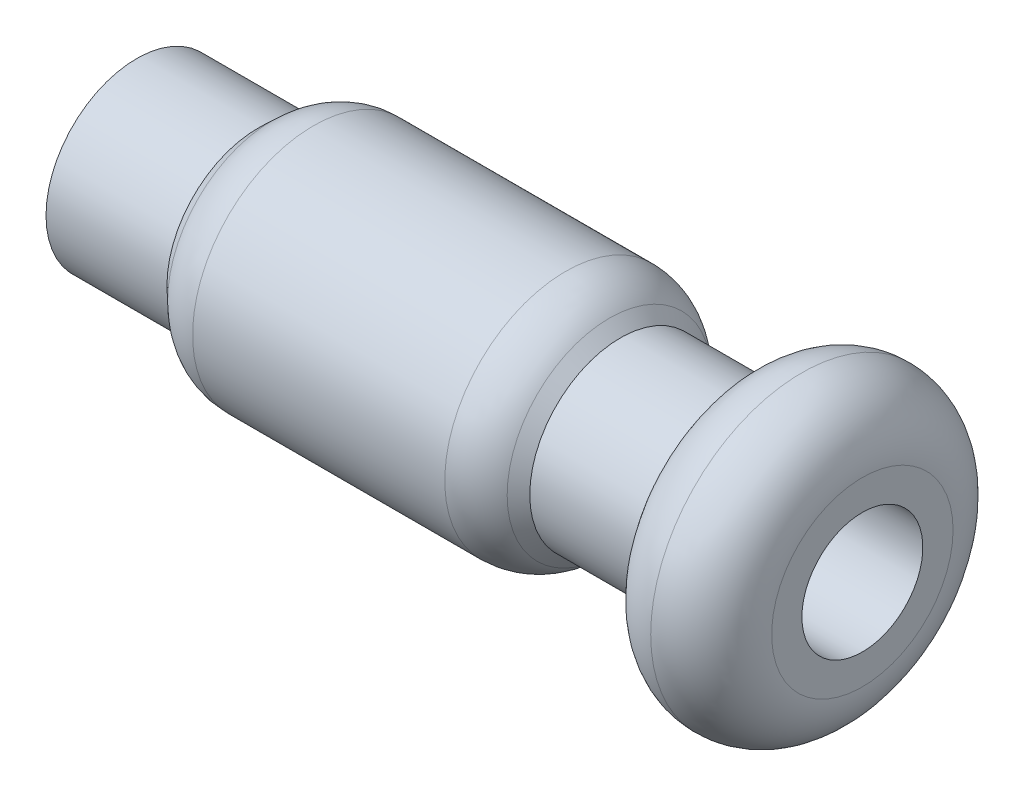
SolidWorks part; units mm, degrees
ref_plane "Front Plane" through (0, 0, 0) normal (0, 0, 1) x (1, 0, 0)
ref_plane "Top Plane" through (0, 0, 0) normal (0, 1, 0) x (1, 0, 0)
ref_plane "Right Plane" through (0, 0, 0) normal (1, 0, 0) x (0, 0, -1)
sketch "Sketch1" plane through (0, 0, 0) normal (0, 0, 1) x (1, 0, 0)
  line L0 (0, 0) -> (10, 0)
  line L1 (10, 0) -> (10, 0.5)
  line L2 (10, 0.5) -> (8, 0.5)
  line L3 (8, 0.5) -> (7.5219, 1)
  line L4 (7.5219, 1) -> (2.5229, 1)
  line L5 (2.5229, 1) -> (2, 0.5)
  line L6 (2, 0.5) -> (0, 0.5)
  line L7 (0, 0.5) -> (0, 0)
  line L8 (-1.4309, -1) -> (12.3178, -1)
  dimension "D1" = 10
  dimension "D2" = 2
  dimension "D3" = 0.5
  dimension "D4" = 1
  dimension "D5" = 1
revolve "Revolve1" add sketch "Sketch1" angle 360 about L8 region at (5.0038, 0.4247, 0)
sketch "Sketch2" plane through (0, 0, 0) normal (0, 0, 1) x (1, 0, 0)
  line L0 (10, -1) -> (12, -1) construction
  line L1 (10, -2.5) -> (10, 0.5) construction
  line L2 (12, -2) -> (12, -3.5)
  line L3 (12, -3.5) -> (10, -3.5)
  line L4 (10, -3.5) -> (10, -2)
  line L5 (10, -2) -> (12, -2)
  point P8 (12.0526, -1)
  point P9 (12.0628, -1)
  dimension "D2" = 1.5
  dimension "D3" = 2
  dimension "D1" = 1
revolve "Revolve2" add sketch "Sketch2" angle 360 about L0
fillet "Fillet1" radius 1 2 edges at (2.5229, -1, 2) (7.5219, -1, 2)
fillet "Fillet2" radius 1 2 edges at (12, -1, 2.5) (10, -1, 2.5)
